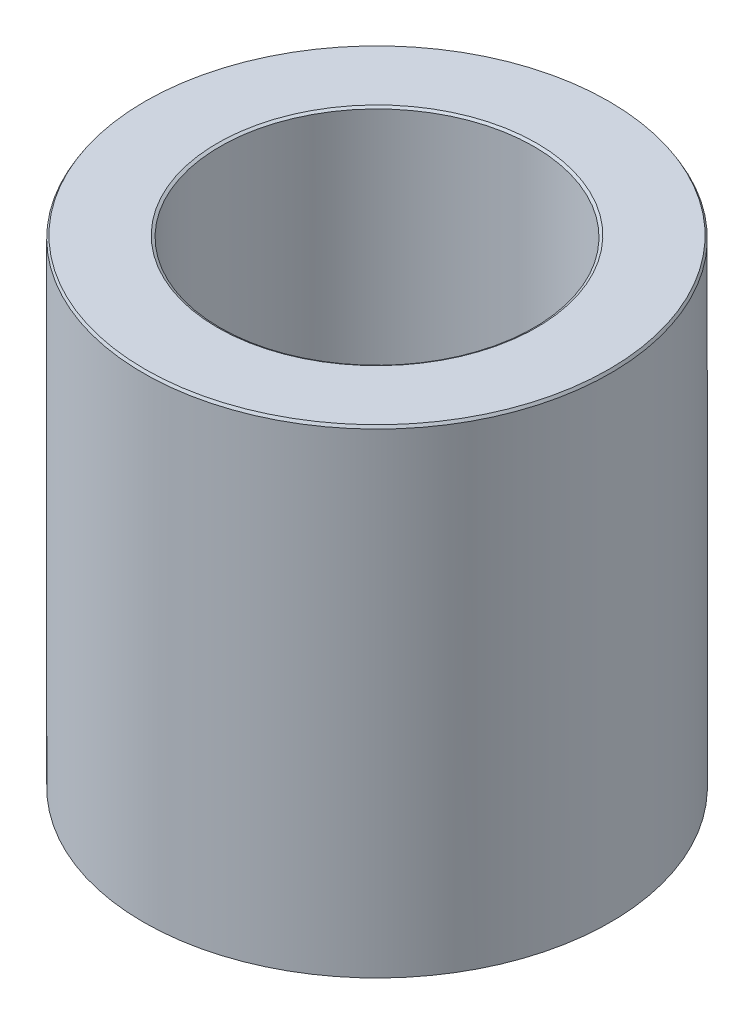
SolidWorks part; units mm, degrees
ref_plane "Front Plane" through (0, 0, 0) normal (0, 0, 1) x (1, 0, 0)
ref_plane "Top Plane" through (0, 0, 0) normal (0, 1, 0) x (1, 0, 0)
ref_plane "Right Plane" through (0, 0, 0) normal (1, 0, 0) x (0, 0, -1)
sketch "Sketch1" plane through (0, 0, 0) normal (0, 1, 0) x (1, 0, 0)
  circle A0 centre (0, 0) radius 30
  dimension "SLEEVE_OD" = 60
extrude "Boss-Extrude1" add sketch "Sketch1" along normal blind 61.5997
sketch "Sketch2" plane through (0, 0, 0) normal (0, 1, 0) x (1, 0, 0)
  circle A0 centre (0, 0) radius 20.1624
  dimension "BORE_D" = 40.3249
extrude "Cut-Extrude1" cut sketch "Sketch2" along normal through all
chamfer "Chamfer1" distance 0.3432 angle 30.509 4 edges at (0, 61.5997, 20.1624) (0, 0, 20.1624) (0, 0, 30) (0, 61.5997, 30) first distance on face at (0, 61.5997, 20.1624) first distance on face at (0, 0, 20.1624) first distance on face at (0, 61.5997, 30)
